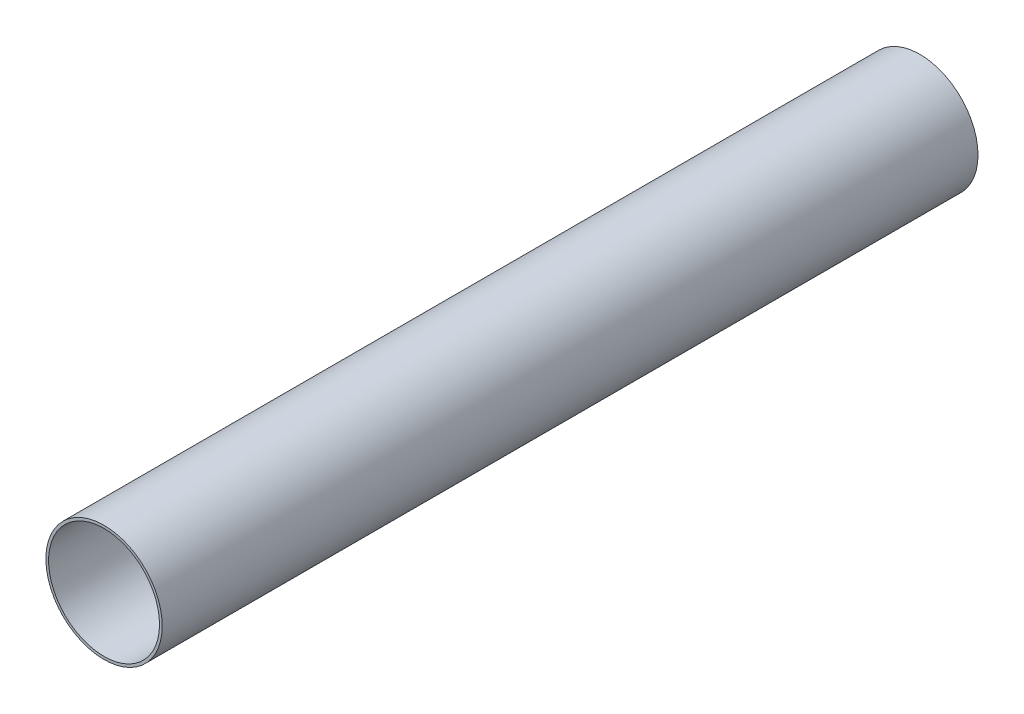
SolidWorks part; units mm, degrees
material "A-Glass Fiber"
ref_plane "Front Plane" through (0, 0, 0) normal (0, 0, 1) x (1, 0, 0)
ref_plane "Top Plane" through (0, 0, 0) normal (0, 1, 0) x (1, 0, 0)
ref_plane "Right Plane" through (0, 0, 0) normal (1, 0, 0) x (0, 0, -1)
sketch "Sketch2" plane through (0, 0, 0) normal (0, 0, 1) x (1, 0, 0)
  circle A0 centre (0, 0) radius 49.2125
  circle A1 centre (0, 0) radius 51.6125
  dimension "D1" = 98.425
  dimension "D2" = 2.4
extrude "Boss-Extrude1" add sketch "Sketch2" along normal blind 362 and the other way blind 362
